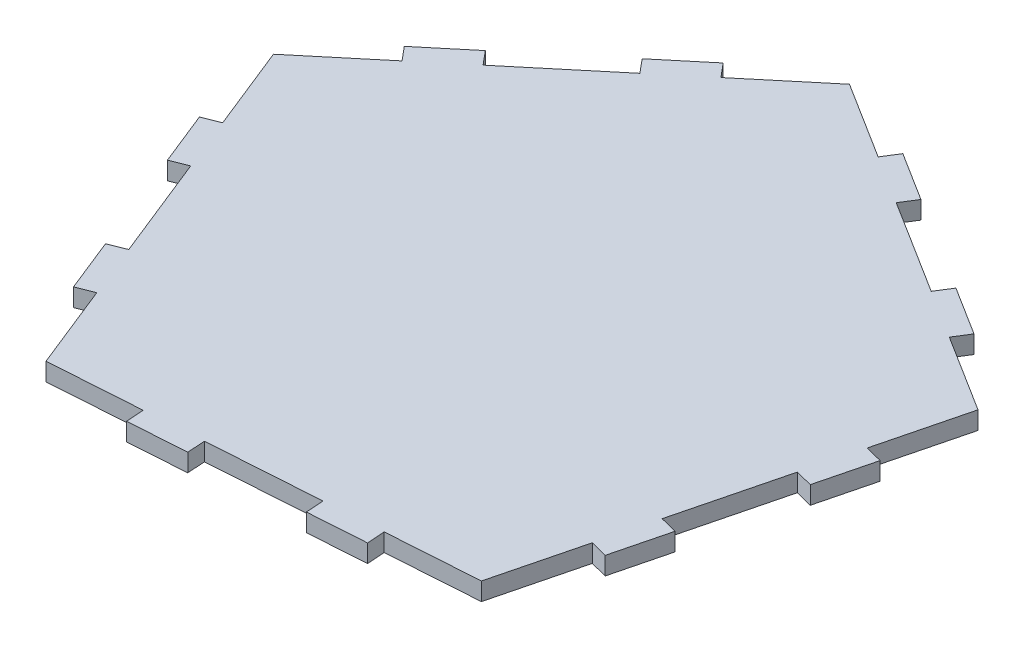
SolidWorks part; units mm, degrees
ref_plane "Front Plane" through (0, 0, 0) normal (0, 0, 1) x (1, 0, 0)
ref_plane "Top Plane" through (0, 0, 0) normal (0, 1, 0) x (1, 0, 0)
ref_plane "Right Plane" through (0, 0, 0) normal (1, 0, 0) x (0, 0, -1)
sketch "Sketch1" plane through (0, 0, 0) normal (0, 1, 0) x (1, 0, 0)
  line L1 (-63.7371, 16.0796) -> (-34.9884, -55.6487)
  line L2 (-34.9884, -55.6487) -> (42.1131, -50.4724)
  line L3 (42.1131, -50.4724) -> (61.0157, 24.4551)
  line L4 (61.0157, 24.4551) -> (-4.4033, 65.5865)
  line L5 (-4.4033, 65.5865) -> (-63.7371, 16.0796)
  circle A0 centre (0, 0) radius 53.18 construction
  dimension "D1" = 106.36
extrude "Boss-Extrude1" add sketch "Sketch1" along normal blind 3.18
sketch "Sketch2" plane through (0, 0, 0) normal (0, -1, 0) x (1, 0, 0)
  line L0 (-56.7625, 1.3223) -> (-53.8107, 0.1392)
  line L1 (-56.7625, 1.3223) -> (-53.124, 10.4003)
  line L2 (-53.8107, 0.1392) -> (-50.1723, 9.2172)
  line L3 (-53.124, 10.4003) -> (-50.1723, 9.2172)
  line L4 (-63.7371, -16.0796) -> (-34.9884, 55.6487) construction
  line L5 (-45.6015, 29.1689) -> (-41.9631, 38.2469)
  line L6 (-45.6015, 29.1689) -> (-42.6498, 27.9858)
  line L7 (-41.9631, 38.2469) -> (-39.0113, 37.0638)
  line L8 (-42.6498, 27.9858) -> (-39.0113, 37.0638)
  line L9 (-49.3628, 19.7846) -> (-19.2439, 7.7129) construction
  line L10 (-43.7823, 33.7079) -> (-40.8306, 32.5248) construction
  dimension "D1" = 3.18
  dimension "D2" = 9.78
  dimension "D3" = 10.11
extrude "Female Cut" [suppressed] cut sketch "Sketch2" against normal through all
ref_axis "Axis1" through (0, 3.339, 0) along (0, -1, 0)
pattern_circular "CirPattern1" [suppressed] count 5 over 360 about axis through (0, 3.339, 0) along (0, -1, 0) of bodies 102
sketch "Sketch3" plane through (0, 3.18, 0) normal (0, 1, 0) x (1, 0, 0)
  line L0 (0, 0) -> (-40.9819, 49.1167) construction
  line L1 (-49.5112, 27.9494) -> (-47.4739, 25.5077)
  line L2 (-49.5112, 27.9494) -> (-41.664, 34.4969)
  line L3 (-47.4739, 25.5077) -> (-39.6267, 32.0552)
  line L4 (-41.664, 34.4969) -> (-39.6267, 32.0552)
  line L5 (-4.4033, 65.5865) -> (-63.7371, 16.0796) construction
  line L6 (-74.0334, 7.4886) -> (-71.9961, 5.0469)
  line L7 (-74.0334, 7.4886) -> (2.7493, 71.5544)
  line L8 (-71.9961, 5.0469) -> (4.7866, 69.1127)
  line L9 (2.7493, 71.5544) -> (4.7866, 69.1127)
  line L14 (-26.4764, 47.1691) -> (-24.4391, 44.7274)
  line L15 (-26.4764, 47.1691) -> (-18.6292, 53.7166)
  line L16 (-24.4391, 44.7274) -> (-16.5919, 51.275)
  line L17 (-18.6292, 53.7166) -> (-16.5919, 51.275)
  line L18 (-45.5876, 31.2231) -> (-43.5503, 28.7815) construction
  line L20 (-9.7247, 57.0048) -> (-11.762, 59.4465) construction
  line M18 (-4.4033, 65.5865) -> (-63.7371, 16.0796)
  line M19 (-63.7371, 16.0796) -> (-34.9884, -55.6487)
  line M22 (61.0157, 24.4551) -> (-4.4033, 65.5865)
  dimension "D1" = 3.18
  dimension "D2" = 10.22
  dimension "D3" = 9.89
  dimension "D4" = 100
extrude "Male Cut" cut sketch "Sketch3" against normal blind 10 contours L8 L1 M19 M18 | L14 L7 L4 L8 | L17 L8 M18 M22 region at (-55.7964, 3.18, -20.6156) region at (-33.0515, 3.18, -39.6122) region at (-10.2882, 3.18, -58.5866)
pattern_circular "CirPattern2" count 5 over 360 about axis through (0, 3.339, 0) along (0, -1, 0) of "Male Cut"
equation "\"kerf\"= .22mm"
equation "\"tabWidthF\"= 10 - \"kerf\""
equation "\"tabThickness\"= 3.18"
equation "\"D1@Sketch2\"=\"tabThickness\""
equation "\"tabWidthM\"= 10 + \"kerf\""
equation "\"halfkerf\"= \"kerf\" / 2.00mm"
equation "\"tabLength\" = \"kerf\" + 12"
